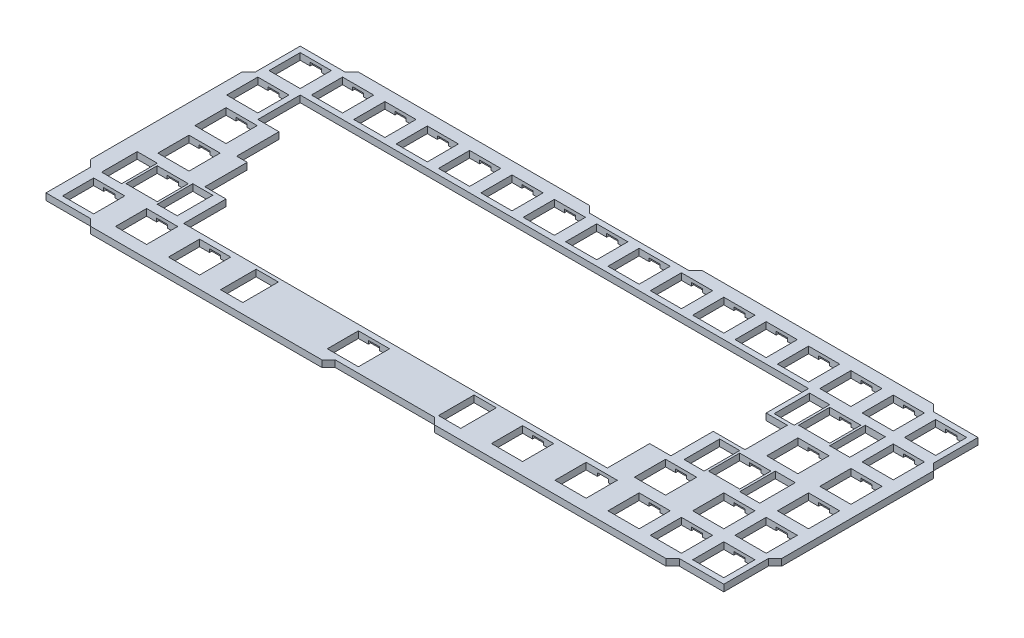
SolidWorks part; units mm, degrees
ref_plane "Front Plane" through (0, 0, 0) normal (0, 0, 1) x (1, 0, 0)
ref_plane "Top Plane" through (0, 0, 0) normal (0, 1, 0) x (1, 0, 0)
ref_plane "Right Plane" through (0, 0, 0) normal (1, 0, 0) x (0, 0, -1)
sketch "Sketch1" plane through (0, 0, 0) normal (0, 1, 0) x (1, 0, 0)
  line L2 (0, 0) -> (0, -19.05)
  line L5 (21.575, -2.525) -> (21.575, -16.525)
  line L6 (2.525, -2.525) -> (16.525, -2.525)
  line L7 (2.525, -2.525) -> (2.525, -16.525)
  line L8 (2.525, -16.525) -> (16.525, -16.525)
  line L9 (16.525, -2.525) -> (16.525, -16.525)
  line L10 (2.525, -2.525) -> (16.525, -16.525) construction
  line L11 (2.525, -16.525) -> (16.525, -2.525) construction
  line L12 (21.575, -2.525) -> (35.575, -2.525)
  line L13 (35.575, -2.525) -> (35.575, -16.525)
  line L14 (21.575, -16.525) -> (35.575, -16.525)
  line L15 (40.625, -2.525) -> (40.625, -16.525)
  line L16 (40.625, -2.525) -> (54.625, -2.525)
  line L17 (54.625, -2.525) -> (54.625, -16.525)
  line L18 (40.625, -16.525) -> (54.625, -16.525)
  line L19 (59.675, -2.525) -> (59.675, -16.525)
  line L20 (59.675, -2.525) -> (73.675, -2.525)
  line L21 (73.675, -2.525) -> (73.675, -16.525)
  line L22 (59.675, -16.525) -> (73.675, -16.525)
  line L23 (78.725, -2.525) -> (78.725, -16.525)
  line L24 (78.725, -2.525) -> (92.725, -2.525)
  line L25 (92.725, -2.525) -> (92.725, -16.525)
  line L26 (78.725, -16.525) -> (92.725, -16.525)
  line L27 (97.775, -2.525) -> (97.775, -16.525)
  line L28 (97.775, -2.525) -> (111.775, -2.525)
  line L29 (111.775, -2.525) -> (111.775, -16.525)
  line L30 (97.775, -16.525) -> (111.775, -16.525)
  line L31 (116.825, -2.525) -> (116.825, -16.525)
  line L32 (116.825, -2.525) -> (130.825, -2.525)
  line L33 (130.825, -2.525) -> (130.825, -16.525)
  line L34 (116.825, -16.525) -> (130.825, -16.525)
  line L35 (135.875, -2.525) -> (135.875, -16.525)
  line L36 (135.875, -2.525) -> (149.875, -2.525)
  line L37 (149.875, -2.525) -> (149.875, -16.525)
  line L38 (135.875, -16.525) -> (149.875, -16.525)
  line L39 (154.925, -2.525) -> (154.925, -16.525)
  line L40 (154.925, -2.525) -> (168.925, -2.525)
  line L41 (168.925, -2.525) -> (168.925, -16.525)
  line L42 (154.925, -16.525) -> (168.925, -16.525)
  line L43 (173.975, -2.525) -> (173.975, -16.525)
  line L44 (173.975, -2.525) -> (187.975, -2.525)
  line L45 (187.975, -2.525) -> (187.975, -16.525)
  line L46 (173.975, -16.525) -> (187.975, -16.525)
  line L47 (193.025, -2.525) -> (193.025, -16.525)
  line L48 (193.025, -2.525) -> (207.025, -2.525)
  line L49 (207.025, -2.525) -> (207.025, -16.525)
  line L50 (193.025, -16.525) -> (207.025, -16.525)
  line L51 (212.075, -2.525) -> (212.075, -16.525)
  line L52 (212.075, -2.525) -> (226.075, -2.525)
  line L53 (226.075, -2.525) -> (226.075, -16.525)
  line L54 (212.075, -16.525) -> (226.075, -16.525)
  line L55 (231.125, -2.525) -> (231.125, -16.525)
  line L56 (231.125, -2.525) -> (245.125, -2.525)
  line L57 (245.125, -2.525) -> (245.125, -16.525)
  line L58 (231.125, -16.525) -> (245.125, -16.525)
  line L59 (250.175, -2.525) -> (250.175, -16.525)
  line L60 (250.175, -2.525) -> (264.175, -2.525)
  line L61 (264.175, -2.525) -> (264.175, -16.525)
  line L62 (250.175, -16.525) -> (264.175, -16.525)
  line L63 (269.225, -2.525) -> (269.225, -16.525)
  line L64 (269.225, -2.525) -> (283.225, -2.525)
  line L65 (283.225, -2.525) -> (283.225, -16.525)
  line L66 (269.225, -16.525) -> (283.225, -16.525)
  line L67 (288.275, -2.525) -> (288.275, -16.525)
  line L68 (288.275, -2.525) -> (302.275, -2.525)
  line L69 (302.275, -2.525) -> (302.275, -16.525)
  line L70 (288.275, -16.525) -> (302.275, -16.525)
  line L71 (302.275, -21.575) -> (302.275, -35.575)
  line L72 (288.275, -21.575) -> (288.275, -35.575)
  line L73 (288.275, -35.575) -> (302.275, -35.575)
  line L74 (288.275, -21.575) -> (302.275, -21.575)
  line L75 (302.275, -40.625) -> (302.275, -54.625)
  line L76 (288.275, -40.625) -> (288.275, -54.625)
  line L77 (288.275, -54.625) -> (302.275, -54.625)
  line L78 (288.275, -40.625) -> (302.275, -40.625)
  line L79 (302.275, -59.675) -> (302.275, -73.675)
  line L80 (288.275, -59.675) -> (288.275, -73.675)
  line L81 (288.275, -73.675) -> (302.275, -73.675)
  line L82 (288.275, -59.675) -> (302.275, -59.675)
  line L83 (302.275, -78.725) -> (302.275, -92.725)
  line L84 (288.275, -78.725) -> (288.275, -92.725)
  line L85 (288.275, -92.725) -> (302.275, -92.725)
  line L86 (288.275, -78.725) -> (302.275, -78.725)
  line L87 (302.275, -97.775) -> (302.275, -111.775)
  line L88 (288.275, -97.775) -> (288.275, -111.775)
  line L89 (288.275, -111.775) -> (302.275, -111.775)
  line L90 (288.275, -97.775) -> (302.275, -97.775)
  line L91 (2.525, -21.575) -> (2.525, -35.575)
  line L92 (2.525, -21.575) -> (16.525, -21.575)
  line L93 (16.525, -21.575) -> (16.525, -35.575)
  line L94 (2.525, -35.575) -> (16.525, -35.575)
  line L95 (0, -19.05) -> (0, -38.1)
  line L97 (19.05, -19.05) -> (19.05, -38.1)
  line L99 (288.275, -97.775) -> (302.275, -111.775)
  line L101 (0, -38.1) -> (0, -57.15)
  line L103 (28.575, -38.1) -> (28.575, -57.15)
  line L107 (33.3375, -57.15) -> (33.3375, -76.2)
  line L111 (42.8625, -76.2) -> (42.8625, -95.25)
  line L113 (0, -95.25) -> (0, -114.3)
  line L116 (283.225, -97.775) -> (283.225, -111.775)
  line L120 (304.8, -95.25) -> (304.8, -114.3)
  line L121 (285.75, -95.25) -> (304.8, -114.3) construction
  line L122 (285.75, -114.3) -> (304.8, -95.25) construction
  line L123 (269.225, -111.775) -> (283.225, -111.775)
  line L124 (269.225, -97.775) -> (269.225, -111.775)
  line L125 (269.225, -97.775) -> (283.225, -97.775)
  line L130 (264.175, -97.775) -> (264.175, -111.775)
  line L131 (250.175, -111.775) -> (264.175, -111.775)
  line L132 (250.175, -97.775) -> (250.175, -111.775)
  line L133 (250.175, -97.775) -> (264.175, -97.775)
  line L140 (4.9063, -97.775) -> (18.9063, -97.775)
  line L141 (4.9063, -97.775) -> (4.9063, -111.775)
  line L142 (4.9063, -111.775) -> (18.9063, -111.775)
  line L143 (18.9063, -97.775) -> (18.9063, -111.775)
  line L144 (4.9063, -97.775) -> (18.9063, -111.775) construction
  line L145 (4.9063, -111.775) -> (18.9063, -97.775) construction
  line L149 (28.7162, -97.775) -> (28.7162, -111.775)
  line L150 (28.7162, -97.775) -> (42.7162, -97.775)
  line L151 (42.7162, -97.775) -> (42.7162, -111.775)
  line L152 (28.7162, -111.775) -> (42.7162, -111.775)
  line L157 (52.5262, -97.775) -> (52.5262, -111.775)
  line L158 (52.5262, -97.775) -> (66.5262, -97.775)
  line L159 (66.5262, -97.775) -> (66.5262, -111.775)
  line L160 (52.5262, -111.775) -> (66.5262, -111.775)
  line L161 (247.65, -38.1) -> (257.175, -38.1)
  line L167 (226.3625, -97.775) -> (240.3625, -97.775)
  line L168 (226.3625, -97.775) -> (226.3625, -111.775)
  line L169 (226.3625, -111.775) -> (240.3625, -111.775)
  line L170 (240.3625, -97.775) -> (240.3625, -111.775)
  line L171 (226.3625, -97.775) -> (240.3625, -111.775) construction
  line L172 (226.3625, -111.775) -> (240.3625, -97.775) construction
  line L176 (197.7825, -97.775) -> (197.7825, -111.775)
  line L177 (197.7825, -97.775) -> (211.7825, -97.775)
  line L178 (211.7825, -97.775) -> (211.7825, -111.775)
  line L179 (197.7825, -111.775) -> (211.7825, -111.775)
  line L180 (19.05, -38.1) -> (28.575, -38.1)
  line L182 (7.2875, -40.625) -> (21.2875, -40.625)
  line L183 (7.2875, -40.625) -> (7.2875, -54.625)
  line L184 (7.2875, -54.625) -> (21.2875, -54.625)
  line L185 (21.2875, -40.625) -> (21.2875, -54.625)
  line L186 (28.575, -57.15) -> (33.3375, -57.15)
  line L187 (0, -57.15) -> (0, -76.2)
  line L188 (0, -76.2) -> (0, -95.25)
  line L189 (9.6688, -59.675) -> (23.6688, -59.675)
  line L190 (9.6688, -59.675) -> (9.6688, -73.675)
  line L191 (9.6688, -73.675) -> (23.6688, -73.675)
  line L192 (23.6688, -59.675) -> (23.6688, -73.675)
  line L193 (9.6688, -59.675) -> (23.6688, -73.675) construction
  line L194 (9.6688, -73.675) -> (23.6688, -59.675) construction
  line L196 (14.4313, -78.725) -> (28.4313, -78.725)
  line L197 (14.4313, -78.725) -> (14.4313, -92.725)
  line L198 (14.4313, -92.725) -> (28.4313, -92.725)
  line L199 (28.4313, -78.725) -> (28.4313, -92.725)
  line L200 (14.4313, -78.725) -> (28.4313, -92.725) construction
  line L201 (14.4313, -92.725) -> (28.4313, -78.725) construction
  line L257 (304.8, 0) -> (304.8, -19.05)
  line L261 (304.8, -19.05) -> (304.8, -38.1)
  line L265 (304.8, -38.1) -> (304.8, -57.15)
  line L269 (304.8, -57.15) -> (304.8, -76.2)
  line L273 (304.8, -76.2) -> (304.8, -95.25)
  line L277 (283.225, -78.725) -> (283.225, -92.725)
  line L279 (247.65, -19.05) -> (247.65, -38.1)
  line L282 (269.225, -92.725) -> (283.225, -92.725)
  line L283 (269.225, -78.725) -> (269.225, -92.725)
  line L284 (269.225, -78.725) -> (283.225, -78.725)
  line L289 (257.175, -57.15) -> (242.8875, -57.15)
  line L293 (233.3625, -76.2) -> (233.3625, -95.25)
  line L297 (242.8875, -76.2) -> (242.8875, -57.15)
  line L301 (257.175, -38.1) -> (257.175, -57.15)
  line L302 (259.7, -21.575) -> (273.7, -21.575)
  line L303 (259.7, -21.575) -> (259.7, -35.575)
  line L304 (259.7, -35.575) -> (273.7, -35.575)
  line L305 (273.7, -21.575) -> (273.7, -35.575)
  line L306 (259.7, -21.575) -> (273.7, -35.575) construction
  line L307 (259.7, -35.575) -> (273.7, -21.575) construction
  line L308 (242.8875, -76.2) -> (233.3625, -76.2)
  line L309 (233.3625, -95.25) -> (190.495, -95.25)
  line L310 (264.4625, -40.625) -> (278.4625, -40.625)
  line L311 (264.4625, -40.625) -> (264.4625, -54.625)
  line L312 (264.4625, -54.625) -> (278.4625, -54.625)
  line L313 (278.4625, -40.625) -> (278.4625, -54.625)
  line L314 (264.4625, -40.625) -> (278.4625, -54.625) construction
  line L315 (264.4625, -54.625) -> (278.4625, -40.625) construction
  line L316 (243.0313, -78.725) -> (257.0313, -78.725)
  line L317 (243.0313, -78.725) -> (243.0313, -92.725)
  line L318 (243.0313, -92.725) -> (257.0313, -92.725)
  line L319 (257.0313, -78.725) -> (257.0313, -92.725)
  line L320 (243.0313, -78.725) -> (257.0313, -92.725) construction
  line L321 (243.0313, -92.725) -> (257.0313, -78.725) construction
  line L322 (33.3375, -76.2) -> (42.8625, -76.2)
  line L323 (257.3188, -59.675) -> (271.3188, -59.675)
  line L324 (257.3188, -59.675) -> (257.3188, -73.675)
  line L325 (257.3188, -73.675) -> (271.3188, -73.675)
  line L326 (271.3188, -59.675) -> (271.3188, -73.675)
  line L327 (257.3188, -59.675) -> (271.3188, -73.675) construction
  line L328 (257.3188, -73.675) -> (271.3188, -59.675) construction
  line L329 (42.8625, -95.25) -> (71.4325, -95.25)
  line L330 (71.4325, -95.25) -> (190.495, -114.3)
  line L331 (0, 0) -> (304.8, 0)
  line L332 (190.495, -114.3) -> (304.8, -114.3)
  line L338 (23.81, -95.25) -> (23.81, -114.3) [skipped]
  line L339 (47.62, -95.25) -> (47.62, -114.3) [skipped]
  line L340 (0, -114.3) -> (71.4325, -114.3)
  line L341 (19.05, -19.05) -> (247.65, -19.05)
  line L345 (71.4325, -114.3) -> (71.4325, -95.25)
  line L347 (190.495, -114.3) -> (190.495, -95.25)
  line L348 (71.4325, -95.25) -> (190.495, -95.25)
  line L349 (71.4325, -95.25) -> (71.4325, -114.3)
  line L350 (71.4325, -114.3) -> (190.495, -114.3)
  line L351 (190.495, -95.25) -> (190.495, -114.3)
  line L353 (123.9638, -97.775) -> (137.9638, -97.775)
  line L354 (123.9638, -97.775) -> (123.9638, -111.775)
  line L355 (123.9638, -111.775) -> (137.9638, -111.775)
  line L356 (137.9638, -97.775) -> (137.9638, -111.775)
  line L357 (123.9638, -97.775) -> (137.9638, -111.775) construction
  line L358 (123.9638, -111.775) -> (137.9638, -97.775) construction
  line L371 (266.7, -95.25) -> (266.7, -114.3) [skipped]
  line L372 (285.75, -95.25) -> (285.75, -114.3) [skipped]
  line L376 (285.75, -76.2) -> (285.75, -95.25) [skipped]
  point P3 (130.9638, -104.775)
  point P5 (9.525, -9.525)
  point P110 (295.275, -104.775)
  point P115 (11.9063, -104.775)
  point P154 (233.3625, -104.775)
  point P172 (16.6688, -66.675)
  point P177 (21.4313, -85.725)
  point P273 (266.7, -28.575)
  point P279 (247.65, -28.575)
  point P280 (271.4625, -47.625)
  point P285 (250.0313, -85.725)
  point P290 (264.3188, -66.675)
  dimension "D2" = 19.05
  dimension "D3" = 14
  dimension "D7" = 28.575
  dimension "D8" = 19.05
  dimension "D9" = 33.3375
  dimension "D10" = 19.05
  dimension "D11" = 42.8625
  dimension "D12" = 19.05
  dimension "D13" = 304.8
  dimension "D14" = 19.05
  dimension "D15" = 71.4325
  dimension "D16" = 5.05
  dimension "D17" = 19.05
  dimension "D18" = 19.05
  dimension "D20" = 14
  dimension "D21" = 14
  dimension "D22" = 19.05
  dimension "D24" = 19.05
  dimension "D25" = 14
  dimension "D26" = 14
  dimension "D28" = 28.575
  dimension "D29" = 19.05
  dimension "D30" = 14.58
  dimension "D31" = 14
  dimension "D32" = 14
  dimension "D33" = 14
  dimension "D34" = 14
  dimension "D35" = 14
  dimension "D36" = 14
  dimension "D40" = 19.05
  dimension "D41" = 19.05
  dimension "D42" = 119.0625
  dimension "D43" = 14
  dimension "D44" = 14
  dimension "D45" = 14
  dimension "D46" = 0
  dimension "D47" = 14
  dimension "D48" = 14
  dimension "D49" = 14
  dimension "D50" = 14
  dimension "D51" = 14
  dimension "D52" = 14
  dimension "D37" = 19.05
  dimension "D53" = 14
  dimension "D4" = 16
  dimension "D5" = 6
  dimension "D6" = 2
  dimension "D19" = 3
  dimension "D23" = 3
  dimension "D27" = 2
  dimension "D38" = 5
  dimension "D39" = 2
extrude "Boss-Extrude1" add sketch "Sketch1" along normal blind 3
sketch "Sketch2" plane through (0, 3, 0) normal (0, 1, 0) x (1, 0, 0)
  line L0 (123.9638, -97.775) -> (123.9638, -111.775) construction
  line L1 (76.9638, -96.775) -> (86.9638, -96.775)
  line L2 (76.9638, -96.775) -> (76.9638, -112.775)
  line L3 (76.9638, -112.775) -> (86.9638, -112.775)
  line L4 (86.9638, -96.775) -> (86.9638, -112.775)
  line L9 (130.9638, -111.775) -> (130.9638, -114.3)
  line L10 (123.9638, -111.775) -> (137.9638, -111.775) construction
  line L11 (0, -114.3) -> (304.8, -114.3) construction
  line L12 (184.9638, -112.775) -> (174.9638, -112.775)
  line L13 (174.9638, -96.775) -> (174.9638, -112.775)
  line L14 (184.9638, -96.775) -> (174.9638, -96.775)
  line L15 (184.9638, -96.775) -> (184.9638, -112.775)
  line L16 (4.4313, -77.725) -> (13.4313, -77.725)
  line L17 (4.4313, -77.725) -> (4.4313, -93.725)
  line L18 (4.4313, -93.725) -> (13.4313, -93.725)
  line L19 (13.4313, -77.725) -> (13.4313, -93.725)
  line L20 (14.4313, -78.725) -> (28.4313, -78.725) construction
  line L21 (21.4313, -78.725) -> (21.4313, -92.725)
  line L22 (14.4313, -92.725) -> (28.4313, -92.725) construction
  line L23 (38.4313, -77.725) -> (38.4313, -93.725)
  line L24 (38.4313, -93.725) -> (29.4313, -93.725)
  line L25 (29.4313, -77.725) -> (29.4313, -93.725)
  line L26 (38.4313, -77.725) -> (29.4313, -77.725)
  line L27 (247.3188, -58.675) -> (256.3188, -58.675)
  line L28 (247.3188, -58.675) -> (247.3188, -74.675)
  line L29 (247.3188, -74.675) -> (256.3188, -74.675)
  line L30 (256.3188, -58.675) -> (256.3188, -74.675)
  line L35 (257.3188, -59.675) -> (271.3188, -59.675) construction
  line L36 (264.3188, -59.675) -> (264.3188, -73.675)
  line L37 (257.3188, -73.675) -> (271.3188, -73.675) construction
  line L38 (281.3188, -58.675) -> (281.3188, -74.675)
  line L39 (281.3188, -74.675) -> (272.3188, -74.675)
  line L40 (272.3188, -58.675) -> (272.3188, -74.675)
  line L41 (281.3188, -58.675) -> (272.3188, -58.675)
  line L42 (249.7, -20.575) -> (258.7, -20.575)
  line L43 (249.7, -20.575) -> (249.7, -36.575)
  line L44 (249.7, -36.575) -> (258.7, -36.575)
  line L45 (258.7, -20.575) -> (258.7, -36.575)
  line L46 (259.7, -21.575) -> (273.7, -21.575) construction
  line L47 (266.7, -21.575) -> (266.7, -35.575)
  line L48 (259.7, -35.575) -> (273.7, -35.575) construction
  line L49 (283.7, -20.575) -> (283.7, -36.575)
  line L50 (283.7, -36.575) -> (274.7, -36.575)
  line L51 (274.7, -20.575) -> (274.7, -36.575)
  line L52 (283.7, -20.575) -> (274.7, -20.575)
  point P10 (86.9638, -104.775)
  point P11 (123.9638, -104.775)
  point P25 (21.4313, -78.725)
  point P45 (264.3188, -59.675)
  point P57 (266.7, -21.575)
  dimension "D1" = 47
  dimension "D2" = 16
  dimension "D3" = 10
  dimension "D4" = 0
  dimension "D5" = 17
  dimension "D6" = 1
  dimension "D7" = 16
  dimension "D8" = 9
  dimension "D9" = 9
  dimension "D10" = 16
  dimension "D11" = 9
  dimension "D12" = 16
  dimension "D13" = 17
  dimension "D14" = 17
  dimension "D15" = 1
  dimension "D16" = 1
extrude "Cut-Extrude1" cut sketch "Sketch2" against normal through all contours L45 L42 L43 L44 | L49 L52 L51 L50 | L38 L41 L40 L39 | L30 L27 L28 L29 | L15 L14 L13 L12 | L4 L1 L2 L3 | L23 L26 L25 L24 | L19 L16 L17 L18
sketch "Sketch3" plane through (0, 0, 0) normal (0, -1, 0) x (1, 0, 0)
  line L0 (288.275, 2.525) -> (302.275, 2.525) construction
  line L1 (297.775, 1.525) -> (292.775, 1.525)
  line L2 (297.775, 1.525) -> (297.775, 17.525)
  line L3 (297.775, 17.525) -> (292.775, 17.525)
  line L4 (292.775, 1.525) -> (292.775, 17.525)
  line L5 (302.275, 2.525) -> (302.275, 16.525) construction
  line L6 (278.725, 1.525) -> (278.725, 17.525)
  line L7 (278.725, 1.525) -> (273.725, 1.525)
  line L8 (273.725, 1.525) -> (273.725, 17.525)
  line L9 (278.725, 17.525) -> (273.725, 17.525)
  line L10 (259.675, 1.525) -> (259.675, 17.525)
  line L11 (259.675, 1.525) -> (254.675, 1.525)
  line L12 (254.675, 1.525) -> (254.675, 17.525)
  line L13 (259.675, 17.525) -> (254.675, 17.525)
  line L14 (240.625, 1.525) -> (240.625, 17.525)
  line L15 (240.625, 1.525) -> (235.625, 1.525)
  line L16 (235.625, 1.525) -> (235.625, 17.525)
  line L17 (240.625, 17.525) -> (235.625, 17.525)
  line L18 (221.575, 1.525) -> (221.575, 17.525)
  line L19 (221.575, 1.525) -> (216.575, 1.525)
  line L20 (216.575, 1.525) -> (216.575, 17.525)
  line L21 (221.575, 17.525) -> (216.575, 17.525)
  line L22 (202.525, 1.525) -> (202.525, 17.525)
  line L23 (202.525, 1.525) -> (197.525, 1.525)
  line L24 (197.525, 1.525) -> (197.525, 17.525)
  line L25 (202.525, 17.525) -> (197.525, 17.525)
  line L26 (183.475, 1.525) -> (183.475, 17.525)
  line L27 (183.475, 1.525) -> (178.475, 1.525)
  line L28 (178.475, 1.525) -> (178.475, 17.525)
  line L29 (183.475, 17.525) -> (178.475, 17.525)
  line L30 (164.425, 1.525) -> (164.425, 17.525)
  line L31 (164.425, 1.525) -> (159.425, 1.525)
  line L32 (159.425, 1.525) -> (159.425, 17.525)
  line L33 (164.425, 17.525) -> (159.425, 17.525)
  line L34 (145.375, 1.525) -> (145.375, 17.525)
  line L35 (145.375, 1.525) -> (140.375, 1.525)
  line L36 (140.375, 1.525) -> (140.375, 17.525)
  line L37 (145.375, 17.525) -> (140.375, 17.525)
  line L38 (126.325, 1.525) -> (126.325, 17.525)
  line L39 (126.325, 1.525) -> (121.325, 1.525)
  line L40 (121.325, 1.525) -> (121.325, 17.525)
  line L41 (126.325, 17.525) -> (121.325, 17.525)
  line L42 (107.275, 1.525) -> (107.275, 17.525)
  line L43 (107.275, 1.525) -> (102.275, 1.525)
  line L44 (102.275, 1.525) -> (102.275, 17.525)
  line L45 (107.275, 17.525) -> (102.275, 17.525)
  line L46 (88.225, 1.525) -> (88.225, 17.525)
  line L47 (88.225, 1.525) -> (83.225, 1.525)
  line L48 (83.225, 1.525) -> (83.225, 17.525)
  line L49 (88.225, 17.525) -> (83.225, 17.525)
  line L50 (69.175, 1.525) -> (69.175, 17.525)
  line L51 (69.175, 1.525) -> (64.175, 1.525)
  line L52 (64.175, 1.525) -> (64.175, 17.525)
  line L53 (69.175, 17.525) -> (64.175, 17.525)
  line L54 (50.125, 1.525) -> (50.125, 17.525)
  line L55 (50.125, 1.525) -> (45.125, 1.525)
  line L56 (45.125, 1.525) -> (45.125, 17.525)
  line L57 (50.125, 17.525) -> (45.125, 17.525)
  line L58 (31.075, 1.525) -> (31.075, 17.525)
  line L59 (31.075, 1.525) -> (26.075, 1.525)
  line L60 (26.075, 1.525) -> (26.075, 17.525)
  line L61 (31.075, 17.525) -> (26.075, 17.525)
  line L62 (12.025, 1.525) -> (12.025, 17.525)
  line L63 (12.025, 1.525) -> (7.025, 1.525)
  line L64 (7.025, 1.525) -> (7.025, 17.525)
  line L65 (12.025, 17.525) -> (7.025, 17.525)
  line L66 (297.775, 20.575) -> (297.775, 36.575)
  line L67 (297.775, 20.575) -> (292.775, 20.575)
  line L68 (292.775, 20.575) -> (292.775, 36.575)
  line L69 (297.775, 36.575) -> (292.775, 36.575)
  line L70 (297.775, 39.625) -> (297.775, 55.625)
  line L71 (297.775, 39.625) -> (292.775, 39.625)
  line L72 (292.775, 39.625) -> (292.775, 55.625)
  line L73 (297.775, 55.625) -> (292.775, 55.625)
  line L74 (297.775, 58.675) -> (297.775, 74.675)
  line L75 (297.775, 58.675) -> (292.775, 58.675)
  line L76 (292.775, 58.675) -> (292.775, 74.675)
  line L77 (297.775, 74.675) -> (292.775, 74.675)
  line L78 (297.775, 77.725) -> (297.775, 93.725)
  line L79 (297.775, 77.725) -> (292.775, 77.725)
  line L80 (292.775, 77.725) -> (292.775, 93.725)
  line L81 (297.775, 93.725) -> (292.775, 93.725)
  line L86 (297.775, 96.775) -> (297.775, 112.775) [skipped]
  line L87 (297.775, 112.775) -> (292.775, 112.775) [skipped]
  line L88 (292.775, 96.775) -> (292.775, 112.775) [skipped]
  line L89 (297.775, 96.775) -> (292.775, 96.775) [skipped]
  line L90 (278.725, 77.725) -> (278.725, 93.725)
  line L91 (278.725, 93.725) -> (273.725, 93.725)
  line L92 (273.725, 77.725) -> (273.725, 93.725)
  line L93 (278.725, 77.725) -> (273.725, 77.725)
  line L94 (278.725, 96.775) -> (278.725, 112.775)
  line L95 (278.725, 112.775) -> (273.725, 112.775)
  line L96 (273.725, 96.775) -> (273.725, 112.775)
  line L97 (278.725, 96.775) -> (273.725, 96.775)
  line L98 (297.775, 96.775) -> (297.775, 112.775)
  line L99 (297.775, 112.775) -> (292.775, 112.775)
  line L100 (292.775, 96.775) -> (292.775, 112.775)
  line L101 (297.775, 96.775) -> (292.775, 96.775)
  line L102 (259.675, 96.775) -> (259.675, 112.775)
  line L103 (259.675, 112.775) -> (254.675, 112.775)
  line L104 (254.675, 96.775) -> (254.675, 112.775)
  line L105 (259.675, 96.775) -> (254.675, 96.775)
  line L106 (12.025, 20.575) -> (12.025, 36.575)
  line L107 (12.025, 36.575) -> (7.025, 36.575)
  line L108 (7.025, 20.575) -> (7.025, 36.575)
  line L109 (12.025, 20.575) -> (7.025, 20.575)
  line L110 (269.2, 20.575) -> (264.2, 20.575)
  line L111 (269.2, 20.575) -> (269.2, 36.575)
  line L112 (269.2, 36.575) -> (264.2, 36.575)
  line L113 (264.2, 20.575) -> (264.2, 36.575)
  line L114 (259.7, 21.575) -> (273.7, 21.575) construction
  line L115 (273.7, 21.575) -> (273.7, 35.575) construction
  line L120 (273.9625, 39.625) -> (268.9625, 39.625)
  line L121 (273.9625, 39.625) -> (273.9625, 55.625)
  line L122 (273.9625, 55.625) -> (268.9625, 55.625)
  line L123 (268.9625, 39.625) -> (268.9625, 55.625)
  line L124 (266.8188, 58.675) -> (261.8188, 58.675)
  line L125 (266.8188, 58.675) -> (266.8188, 74.675)
  line L126 (266.8188, 74.675) -> (261.8188, 74.675)
  line L127 (261.8188, 58.675) -> (261.8188, 74.675)
  line L128 (252.5313, 77.725) -> (247.5313, 77.725)
  line L129 (252.5313, 77.725) -> (252.5313, 93.725)
  line L130 (252.5313, 93.725) -> (247.5313, 93.725)
  line L131 (247.5313, 77.725) -> (247.5313, 93.725)
  line L132 (236.3915, 96.0429) -> (231.3915, 96.0429)
  line L133 (236.3915, 96.0429) -> (236.3915, 112.0429)
  line L134 (236.3915, 112.0429) -> (231.3915, 112.0429)
  line L135 (231.3915, 96.0429) -> (231.3915, 112.0429)
  line L136 (207.2825, 96.775) -> (202.2825, 96.775)
  line L137 (207.2825, 96.775) -> (207.2825, 112.775)
  line L138 (207.2825, 112.775) -> (202.2825, 112.775)
  line L139 (202.2825, 96.775) -> (202.2825, 112.775)
  line L140 (133.4638, 96.775) -> (128.4638, 96.775)
  line L141 (133.4638, 96.775) -> (133.4638, 112.775)
  line L142 (133.4638, 112.775) -> (128.4638, 112.775)
  line L143 (128.4638, 96.775) -> (128.4638, 112.775)
  line L144 (62.0262, 96.775) -> (57.0262, 96.775)
  line L145 (62.0262, 96.775) -> (62.0262, 112.775)
  line L146 (62.0262, 112.775) -> (57.0262, 112.775)
  line L147 (57.0262, 96.775) -> (57.0262, 112.775)
  line L148 (38.2163, 96.775) -> (33.2162, 96.775)
  line L149 (38.2163, 96.775) -> (38.2163, 112.775)
  line L150 (38.2163, 112.775) -> (33.2162, 112.775)
  line L151 (33.2162, 96.775) -> (33.2162, 112.775)
  line L152 (14.4063, 96.775) -> (9.4063, 96.775)
  line L153 (14.4063, 96.775) -> (14.4063, 112.775)
  line L154 (14.4063, 112.775) -> (9.4063, 112.775)
  line L155 (9.4063, 96.775) -> (9.4063, 112.775)
  line L156 (23.9313, 77.725) -> (18.9313, 77.725)
  line L157 (23.9313, 77.725) -> (23.9313, 93.725)
  line L158 (23.9313, 93.725) -> (18.9313, 93.725)
  line L159 (18.9313, 77.725) -> (18.9313, 93.725)
  line L160 (19.1688, 58.675) -> (14.1688, 58.675)
  line L161 (19.1688, 58.675) -> (19.1688, 74.675)
  line L162 (19.1688, 74.675) -> (14.1688, 74.675)
  line L163 (14.1688, 58.675) -> (14.1688, 74.675)
  line L164 (16.7875, 39.625) -> (11.7875, 39.625)
  line L165 (16.7875, 39.625) -> (16.7875, 55.625)
  line L166 (16.7875, 55.625) -> (11.7875, 55.625)
  line L167 (11.7875, 39.625) -> (11.7875, 55.625)
  line L168 (264.4625, 40.625) -> (278.4625, 40.625) construction
  line L169 (278.4625, 40.625) -> (278.4625, 54.625) construction
  line L171 (257.3188, 59.675) -> (271.3188, 59.675) construction
  line L172 (271.3188, 59.675) -> (271.3188, 73.675) construction
  line L173 (243.0313, 78.725) -> (257.0313, 78.725) construction
  line L174 (257.0313, 78.725) -> (257.0313, 92.725) construction
  line L175 (197.7825, 97.775) -> (211.7825, 97.775) construction
  line L176 (211.7825, 97.775) -> (211.7825, 111.775) construction
  line L177 (123.9638, 97.775) -> (137.9638, 97.775) construction
  line L178 (123.9638, 97.775) -> (123.9638, 111.775) construction
  line L179 (52.5262, 111.775) -> (66.5262, 111.775) construction
  line L180 (66.5262, 97.775) -> (66.5262, 111.775) construction
  line L181 (28.7162, 97.775) -> (42.7162, 97.775) construction
  line L182 (42.7162, 97.775) -> (42.7162, 111.775) construction
  line L183 (4.9063, 97.775) -> (18.9063, 97.775) construction
  line L184 (4.9063, 97.775) -> (4.9063, 111.775) construction
  line L185 (14.4313, 78.725) -> (28.4313, 78.725) construction
  line L186 (28.4313, 78.725) -> (28.4313, 92.725) construction
  line L187 (9.6688, 59.675) -> (23.6688, 59.675) construction
  line L188 (23.6688, 59.675) -> (23.6688, 73.675) construction
  line L189 (7.2875, 40.625) -> (21.2875, 40.625) construction
  line L190 (21.2875, 40.625) -> (21.2875, 54.625) construction
  point P6 (295.275, 2.525)
  dimension "D1" = 5
  dimension "D2" = 16
  dimension "D3" = 1
  dimension "D4" = 4.5
  dimension "D11" = 5
  dimension "D12" = 16
  dimension "D13" = 1
  dimension "D14" = 4.5
  dimension "D15" = 5
  dimension "D16" = 16
  dimension "D17" = 1
  dimension "D18" = 4.5
  dimension "D19" = 5
  dimension "D20" = 16
  dimension "D21" = 1
  dimension "D22" = 4.5
  dimension "D23" = 5
  dimension "D24" = 16
  dimension "D25" = 1
  dimension "D26" = 4.5
  dimension "D27" = 5
  dimension "D28" = 16
  dimension "D29" = 1
  dimension "D30" = 4.5
  dimension "D31" = 5
  dimension "D32" = 16
  dimension "D33" = 1
  dimension "D34" = 4.5
  dimension "D35" = 5
  dimension "D36" = 16
  dimension "D37" = 1
  dimension "D38" = 4.5
  dimension "D39" = 5
  dimension "D40" = 16
  dimension "D41" = 1
  dimension "D42" = 4.5
  dimension "D43" = 1
  dimension "D44" = 4.5
  dimension "D45" = 5
  dimension "D46" = 16
  dimension "D47" = 1
  dimension "D48" = 5
  dimension "D49" = 16
  dimension "D50" = 4.5
  dimension "D51" = 1
  dimension "D52" = 16
  dimension "D53" = 5
  dimension "D54" = 4.5
  dimension "D55" = 1
  dimension "D56" = 16
  dimension "D57" = 4.5
  dimension "D58" = 5
  dimension "D5" = 16
  dimension "D6" = 6
  dimension "D7" = 2
  dimension "D8" = 2
  dimension "D9" = 2
  dimension "D10" = 2
extrude "Cut-Extrude2" cut sketch "Sketch3" against normal blind 1.5
sketch "Sketch4" plane through (0, 0, 114.3) normal (0, 0, 1) x (1, 0, 0)
  line L0 (0, 3) -> (304.8, 3) construction
  line L1 (20, 3) -> (130, 3)
  line L2 (20, 3) -> (20, 0)
  line L3 (20, 0) -> (130, 0)
  line L4 (130, 3) -> (130, 0)
  line L5 (0, 0) -> (304.8, 0) construction
  line L6 (0, 3) -> (0, 0) construction
  line L7 (304.8, 3) -> (304.8, 0) construction
  line L8 (284.8, 3) -> (174.8, 3)
  line L9 (284.8, 3) -> (284.8, 0)
  line L10 (284.8, 0) -> (174.8, 0)
  line L11 (174.8, 3) -> (174.8, 0)
  dimension "D1" = 110
  dimension "D2" = 20
  dimension "D3" = 110
  dimension "D4" = 20
extrude "Boss-Extrude2" add sketch "Sketch4" along normal blind 3
sketch "Sketch5" plane through (0, 0, 0) normal (0, 0, -1) x (-1, 0, 0)
  line L0 (0, 0) -> (-304.8, 0) construction
  line L1 (-20, 0) -> (-130, 0)
  line L2 (-20, 0) -> (-20, 3)
  line L3 (-20, 3) -> (-130, 3)
  line L4 (-130, 0) -> (-130, 3)
  line L5 (0, 3) -> (-304.8, 3) construction
  line L6 (0, 3) -> (0, 0) construction
  line L7 (-304.8, 3) -> (-304.8, 0) construction
  line L8 (-284.8, 0) -> (-174.8, 0)
  line L9 (-284.8, 0) -> (-284.8, 3)
  line L10 (-284.8, 3) -> (-174.8, 3)
  line L11 (-174.8, 0) -> (-174.8, 3)
  dimension "D1" = 110
  dimension "D2" = 20
  dimension "D3" = 110
  dimension "D4" = 20
extrude "Boss-Extrude3" add sketch "Sketch5" along normal blind 3
sketch "Sketch6" plane through (304.8, 0, 0) normal (1, 0, 0) x (0, 0, -1)
  line L0 (0, 3) -> (-114.3, 3) construction
  line L1 (-94.3, 3) -> (-20, 3)
  line L2 (-94.3, 3) -> (-94.3, 0)
  line L3 (-94.3, 0) -> (-20, 0)
  line L4 (-20, 3) -> (-20, 0)
  line L5 (0, 0) -> (-114.3, 0) construction
  line L6 (-114.3, 0) -> (-114.3, 3) construction
  line L7 (0, 3) -> (0, 0) construction
  dimension "D1" = 20
  dimension "D2" = 20
extrude "Boss-Extrude4" add sketch "Sketch6" along normal blind 3
sketch "Sketch7" plane through (0, 0, 0) normal (-1, 0, 0) x (0, 0, 1)
  line L0 (0, 3) -> (114.3, 3) construction
  line L1 (20, 3) -> (94.3, 3)
  line L2 (20, 3) -> (20, 0)
  line L3 (20, 0) -> (94.3, 0)
  line L4 (94.3, 3) -> (94.3, 0)
  line L5 (0, 0) -> (114.3, 0) construction
  line L6 (0, 3) -> (0, 0) construction
  line L7 (114.3, 3) -> (114.3, 0) construction
  dimension "D1" = 20
  dimension "D2" = 20
extrude "Boss-Extrude5" add sketch "Sketch7" along normal blind 3
chamfer "Chamfer3" distance 3 angle 45 12 edges at (307.8, 1.5, 94.3) (307.8, 1.5, 20) (174.8, 1.5, -3) (284.8, 1.5, -3) (20, 1.5, -3) (130, 1.5, -3) (284.8, 1.5, 117.3) (174.8, 1.5, 117.3) (130, 1.5, 117.3) (20, 1.5, 117.3) (-3, 1.5, 20) (-3, 1.5, 94.3)
